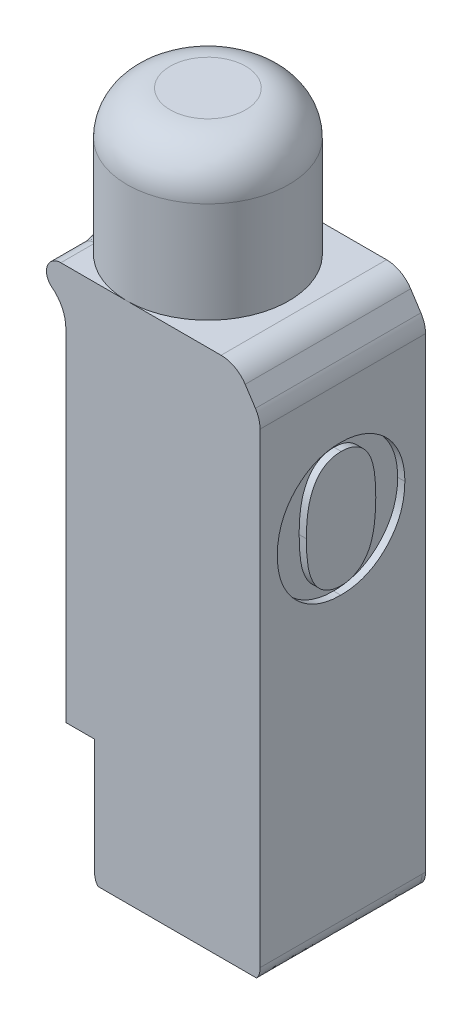
SolidWorks part; units mm, degrees
ref_plane "Přední rovina" through (0, 0, 0) normal (0, 0, 1) x (1, 0, 0)
ref_plane "Horní rovina" through (0, 0, 0) normal (0, 1, 0) x (1, 0, 0)
ref_plane "Pravá rovina" through (0, 0, 0) normal (1, 0, 0) x (0, 0, -1)
sketch "Skica1" plane through (0, 0, 0) normal (0, 0, 1) x (1, 0, 0)
  line L0 (-224.5983, 0) -> (11005.3146, 0) construction
  line L1 (0, -224.5983) -> (0, 11005.3146) construction
  line L3 (-2.3, 0) -> (2.3, 0) construction
  line L4 (-2.3, 0) -> (-2.3, -3.6)
  line L5 (-2.3, -3.6) -> (2.3, -3.6)
  line L6 (2.3, 0) -> (2.3, -3.6)
  line L7 (-2.3, 0) -> (2.3, -3.6) construction
  line L8 (-2.3, -3.6) -> (2.3, 0) construction
  line L9 (-2.3, 10) -> (2.3, 10) construction
  line L10 (-2.3, 10) -> (-2.3, 0) construction
  line L11 (-2.3, 0) -> (2.3, 0) construction
  line L12 (2.3, 10) -> (2.3, 0)
  line L13 (-2.3, 10) -> (2.3, 0) construction
  line L14 (-2.3, 0) -> (2.3, 10) construction
  line L17 (-3.65, 15) -> (0.85, 15)
  line L18 (-3.65, 15) -> (-3.65, 11)
  line L19 (-3.65, 11) -> (0.85, 11) construction
  line L20 (0.85, 15) -> (0.85, 11)
  line L21 (-3.65, 15) -> (0.85, 11) construction
  line L22 (-3.65, 11) -> (0.85, 15) construction
  line L24 (-1.4, -992.1425) -> (-1.4, 49007.8575) construction
  line L25 (-2.3, 10) -> (-3.1, 10) construction
  line L27 (-2.3, 10) -> (-2.3, 0) construction
  line L28 (-2.3, 0) -> (-3.1, 0)
  line L29 (-3.1, 10) -> (-3.1, 0)
  line L30 (-3.1, 10) -> (-4.45, 11)
  line L31 (-4.45, 11) -> (-3.65, 11)
  line L32 (2.3, 10) -> (1.65, 11)
  line L33 (1.65, 11) -> (0.85, 11)
  point P4 (0, -1.8)
  point P10 (-1.4, 13)
  point P12 (0, 5)
  dimension "D1" = 3.6
  dimension "D2" = 4.6
  dimension "D3" = 4.6
  dimension "D4" = 10
  dimension "D5" = 4.5
  dimension "D6" = 4
  dimension "D7" = 1.4
  dimension "D8" = 0.8
  dimension "D9" = 1
  dimension "D10" = 0.8
extrude "Přidat vysunutím1" add sketch "Skica1" along normal blind 4.6
sketch "Skica2" plane through (0, 0, 4.6) normal (0, 0, 1) x (1, 0, 0)
  line L1 (2.3, 10) -> (1.65, 11) construction
  line L2 (1.65, 11) -> (0.85, 11) construction
  line L4 (-3.1, 10) -> (-3.1, 0) construction
  line L10 (-3.1, 10) -> (-3.1, 0)
  line L13 (-3.1, 0) -> (2.3, 0)
  line L14 (-3.65, 11) -> (-4.45, 11) construction
  line L15 (-4.45, 11) -> (-3.1, 10) construction
  line L16 (2.3, 10) -> (1.65, 11)
  line L17 (1.65, 11) -> (0.85, 11)
  line L18 (-3.65, 11) -> (-4.45, 11)
  line L19 (-4.45, 11) -> (-3.1, 10)
  line L20 (-3.65, 11) -> (0.85, 11)
  line L21 (2.3, 0) -> (2.3, 10)
extrude "Přidat vysunutím2" add sketch "Skica2" along normal blind 0.8
sketch "Skica4" plane through (0, 15, 0) normal (0, 1, 0) x (1, 0, 0)
  line L0 (-1002.2, -2.25) -> (48997.8, -2.25) construction
  line L2 (-1.4, -1000) -> (-1.4, 49000) construction
  line L3 (0.85, -4.6) -> (-3.65, -4.6) construction
  line L4 (0.85, -4.6) -> (0.85, 0) construction
  line L5 (0.85, 0) -> (-3.65, 0) construction
  line L6 (-3.65, -4.6) -> (-3.65, 0) construction
  line L7 (0.85, -4.6) -> (-3.65, -4.6)
  line L8 (0.85, -4.6) -> (0.85, 0)
  line L9 (0.85, 0) -> (-3.65, 0)
  line L10 (-3.65, -4.6) -> (-3.65, 0)
  line L11 (0, -1000) -> (0, 49000) construction
  circle A0 centre (-1.4, -2.25) radius 2.25
  line M1 (0.85, 0) -> (-3.65, 0)
  line M2 (-3.65, 0) -> (-3.65, -4.6)
  line M3 (-3.65, -4.6) -> (0.85, -4.6)
  line M4 (0.85, -4.6) -> (0.85, 0)
  dimension "D1" = 4.5
  dimension "D2" = 1.4
extrude "Odebrat vysunutím1" cut sketch "Skica4" against normal up to surface (4 mm away) contours A0 M2 M3 M4 | A0 M4 M1 M2 | A0 M4 M1 region at (-1.4, 15, 4.5492) region at (0.3474, 15, 0.5026) region at (-3.1474, 15, 0.5026) up to face at (-1.4, 11, 2.5)
fillet "Zaoblit4" radius 0.4 3 edges at (-2.3, -3.6, 2.3) (0, -3.6, 4.6) (2.3, -3.6, 2.3) conic rho 0.5
fillet "Zaoblit5" radius 1.2 1 edges at (-1.4, 15, 4.5)
fillet "Zaoblit6" radius 1 1 edges at (-3.1, 10, 2.7)
fillet "Zaoblit7" radius 0.4 1 edges at (-4.45, 11, 2.7)
fillet "Zaoblit8" radius 0.8 2 edges at (1.65, 11, 2.7) (2.3, 10, 2.7)
sketch "Skica5" plane through (0, 0, 0) normal (0, 0, -1) x (-1, 0, 0)
  line L0 (2.3, 0) -> (-2.3, 0)
  line L1 (-2.3, -3.2) -> (-2.3, 9.7628) construction
  line L2 (-2.3, 0) -> (-2.3, 9.7628)
  line L8 (1.4, 11) -> (-1.2159, 11)
  line L9 (-1.8866, 10.636) -> (-2.1708, 10.1988)
  line L10 (-2.3, 9.7628) -> (-2.3, -3.2)
  line L11 (-1.9, -3.6) -> (1.9, -3.6)
  line L12 (2.3, -3.2) -> (2.3, 0)
  line L13 (2.3, 0) -> (3.1, 0)
  line L14 (3.1, 0) -> (3.1, 9.4963)
  line L15 (3.2387, 11) -> (1.4, 11)
  line L16 (1.4, 11) -> (-1.2159, 11)
  line L17 (-1.8866, 10.636) -> (-2.1708, 10.1988)
  line L21 (2.3, 0) -> (3.1, 0)
  line L22 (3.1, 0) -> (3.1, 9.4963)
  line L23 (3.2387, 11) -> (1.4, 11)
  arc A4 (-1.2159, 11) -> (-1.8866, 10.636) centre (-1.2159, 10.2) ccw
  arc A5 (-2.1708, 10.1988) -> (-2.3, 9.7628) centre (-1.5, 9.7628) ccw
  arc A6 (3.4848, 10.2846) -> (3.1, 9.4963) centre (4.1, 9.4963) ccw
  arc A7 (3.4848, 10.2846) -> (3.2387, 11) centre (3.2387, 10.6) ccw
  arc A8 (-1.2159, 11) -> (-1.8866, 10.636) centre (-1.2159, 10.2) ccw
  arc A9 (-2.1708, 10.1988) -> (-2.3, 9.7628) centre (-1.5, 9.7628) ccw
  arc A10 (3.4848, 10.2846) -> (3.1, 9.4963) centre (4.1, 9.4963) ccw
  arc A11 (3.4848, 10.2846) -> (3.2387, 11) centre (3.2387, 10.6) ccw
  parabola Q2 (-2.3, -3.2) -> (-1.9, -3.6) focus (-2.1, -3.4) apex (-2.2, -3.5)
  parabola Q3 (1.9, -3.6) -> (2.3, -3.2) focus (2.1, -3.4) apex (2.2, -3.5)
  dimension "D1" = 0
extrude "Přidat vysunutím3" add sketch "Skica5" along normal blind 0.8
sketch "Skica7" plane through (0, 11, 0) normal (0, 1, 0) x (1, 0, 0)
  line L0 (-1001.2237, -4.5) -> (48998.7763, -4.5) construction
  line L1 (-3.6387, -3.5468) -> (-3.6387, -5.4) construction
  line L2 (2.3, -5.4) -> (-3.6387, -5.4)
  line L3 (2.3, -5.4) -> (2.3, -4.5)
  line L4 (2.3, -4.5) -> (-3.6387, -4.5)
  line L5 (-3.6387, -5.4) -> (-3.6387, -4.5)
  line L6 (-1001.1851, 0) -> (48998.8149, 0) construction
  line L7 (-3.6387, 0.8) -> (-3.6387, -0.9532) construction
  line L8 (-3.6387, 0.8) -> (-3.6387, 0)
  line L10 (-3.6387, 0.8) -> (2.3, 0.8)
  line L11 (2.3, 0.8) -> (2.3, 0)
  line L12 (-3.6387, 0) -> (2.3, 0)
  arc A0 (-3.2387, -3.5468) -> (-3.2387, -0.9532) centre (-1.4, -2.25) ccw construction
extrude "Odebrat vysunutím3" cut sketch "Skica7" against normal through all
sketch "Skica8" plane through (0, 0, 0) normal (0, 0, -1) x (-1, 0, 0)
  line L4 (2.3, 0) -> (3.1, 0)
  line L5 (-2.3, 9.7628) -> (-2.3, -3.2)
  line L6 (-1.9, -3.6) -> (1.9, -3.6)
  line L7 (2.3, -3.2) -> (2.3, 0)
  line L8 (2.3, 0) -> (3.1, 0)
  line L9 (-2.3, 9.7628) -> (-2.3, -3.2)
  line L10 (-1.9, -3.6) -> (1.9, -3.6)
  line L11 (2.3, -3.2) -> (2.3, 0)
  line L16 (3.1, 0) -> (3.1, 9.4963)
  line L17 (3.1, 0) -> (3.1, 9.4963)
  line L18 (3.2387, 11) -> (1.4, 11)
  line L19 (3.2387, 11) -> (1.4, 11)
  line L20 (1.4, 11) -> (-1.2159, 11)
  line L21 (1.4, 11) -> (-1.2159, 11)
  line L22 (-1.8866, 10.636) -> (-2.1708, 10.1988)
  line L23 (-1.8866, 10.636) -> (-2.1708, 10.1988)
  arc A4 (3.4848, 10.2846) -> (3.1, 9.4963) centre (4.1, 9.4963) ccw
  arc A5 (3.4848, 10.2846) -> (3.1, 9.4963) centre (4.1, 9.4963) ccw
  arc A6 (3.4848, 10.2846) -> (3.2387, 11) centre (3.2387, 10.6) ccw
  arc A7 (3.4848, 10.2846) -> (3.2387, 11) centre (3.2387, 10.6) ccw
  arc A8 (-1.2159, 11) -> (-1.8866, 10.636) centre (-1.2159, 10.2) ccw
  arc A9 (-1.2159, 11) -> (-1.8866, 10.636) centre (-1.2159, 10.2) ccw
  arc A10 (-2.1708, 10.1988) -> (-2.3, 9.7628) centre (-1.5, 9.7628) ccw
  arc A11 (-2.1708, 10.1988) -> (-2.3, 9.7628) centre (-1.5, 9.7628) ccw
  parabola Q2 (-2.3, -3.2) -> (-1.9, -3.6) focus (-2.1, -3.4) apex (-2.2, -3.5)
  parabola Q3 (1.9, -3.6) -> (2.3, -3.2) focus (2.1, -3.4) apex (2.2, -3.5)
  parabola Q4 (-2.3, -3.2) -> (-1.9, -3.6) focus (-2.1, -3.4) apex (-2.2, -3.5)
  parabola Q5 (1.9, -3.6) -> (2.3, -3.2) focus (2.1, -3.4) apex (2.2, -3.5)
  dimension "D1" = 0
extrude "Přidat vysunutím4" add sketch "Skica8" along normal blind 0.1
sketch "Skica9" plane through (-3.1, 0, 3) normal (1, 0, 0) x (0, 0, -1)
  text T0 "I" font "Century Schoolbook" height 3.5
extrude "Odebrat vysunutím4" cut sketch "Skica9" along normal blind 0.2
sketch "Skica11" plane through (2.3, 0, 0) normal (1, 0, 0) x (0, 0, -1)
  text T0 "O" font "Century Schoolbook" height 3.5
extrude "Odebrat vysunutím5" cut sketch "Skica11" against normal blind 0.2
